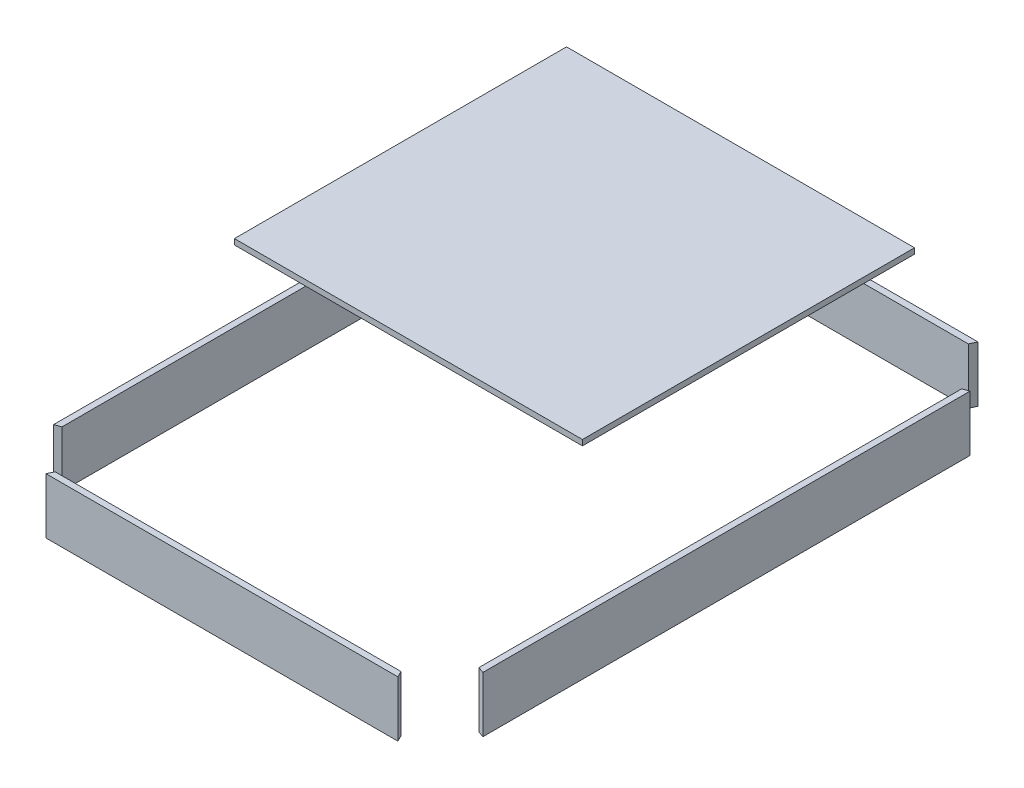
SolidWorks part; units mm, degrees
material "ABS"
ref_plane "Front Plane" through (0, 0, 0) normal (0, 0, 1) x (1, 0, 0)
ref_plane "Top Plane" through (0, 0, 0) normal (0, 1, 0) x (1, 0, 0)
ref_plane "Right Plane" through (0, 0, 0) normal (1, 0, 0) x (0, 0, -1)
sketch "Sketch2" plane through (0, 0, 0) normal (1, 0, 0) x (0, 0, -1)
  line L0 (0, 0) -> (-114.3, 0)
  line L1 (-114.3, 0) -> (-114.3, 25.4)
  line L2 (-114.3, 25.4) -> (-25.4, 50.8)
  line L3 (-25.4, 50.8) -> (94.742, 50.8)
  line L4 (114.3, 25.4) -> (114.3, 0)
  line L5 (114.3, 0) -> (0, 0)
  line L6 (-114.3, 25.4) -> (-114.3, 50.8)
  line L7 (-114.3, 50.8) -> (-25.4, 50.8)
  line L8 (114.3, 25.4) -> (94.742, 50.8)
  dimension "D1" = 25.4
  dimension "D2" = 25.4
  dimension "D3" = 114.3
  dimension "D4" = 114.3
  dimension "D5" = 88.9
  dimension "D6" = 94.742
ref_plane "Plane1" through (0, 25.4, 0) normal (0, 1, 0) x (1, 0, 0)
sketch "Sketch3" plane through (0, 25.4, 0) normal (0, 1, 0) x (1, 0, 0)
  line L0 (-34.4732, 114.3) -> (34.4732, 114.3)
  line L1 (0, 114.3) -> (0, 0) construction
  line L2 (50.8, 94.8425) -> (50.8, -94.8425)
  line L3 (50.8, -94.8425) -> (34.4732, -114.3)
  line L4 (34.4732, -114.3) -> (-34.4732, -114.3)
  line L5 (0, -114.3) -> (0, -25.4) construction
  line L6 (0, 114.3) -> (0, -114.3) construction
  line L7 (-50.8, -94.8425) -> (-34.4732, -114.3)
  line L8 (-50.8, 94.8425) -> (-50.8, -94.8425)
  line L9 (0, -114.3) -> (0, -95.25) construction
  line L10 (0, -95.25) -> (2.7232, -95.25) construction
  line L11 (2.7232, -95.25) -> (2.7232, -87.6586) construction
  line L12 (2.7232, -87.6586) -> (19.05, -68.2011) construction
  line L13 (19.05, -68.2011) -> (31.75, -68.2011) construction
  line L14 (31.75, -68.2011) -> (31.75, 0) construction
  line L15 (31.75, 0) -> (50.8, 0) construction
  line L16 (2.7232, -87.6586) -> (34.4732, -114.3) construction
  line L17 (19.05, -68.2011) -> (50.8, -94.8425) construction
  line L18 (0, 0) -> (-52.6953, 0) construction
  line L19 (50.8, 94.8425) -> (34.4732, 114.3)
  line L20 (-50.8, 94.8425) -> (-34.4732, 114.3)
  dimension "D1" = 101.6
  dimension "D2" = 12.7
  dimension "D3" = 40
  dimension "D4" = 19.05
  dimension "D5" = 19.05
  dimension "D6" = 25.4
ref_plane "Plane4" through (0, 0, -94.742) normal (0, 0, 1) x (1, 0, 0)
ref_plane "Plane2" through (0, 50.8, 0) normal (0, 1, 0) x (1, 0, 0)
sketch "Sketch4" plane through (0, 50.8, 0) normal (0, 1, 0) x (1, 0, 0)
  line L0 (-31.75, 94.742) -> (31.75, 94.742)
  line L1 (31.75, 94.742) -> (31.75, -25.4)
  line L3 (31.75, -25.4) -> (-31.75, -25.4)
  line L4 (0, 0) -> (0, -114.3) construction
  line L5 (0, 114.3) -> (0, -25.4) construction
  line L6 (-31.75, 94.742) -> (-31.75, -25.4)
  line L10 (31.75, -68.2011) -> (31.75, 0) construction
  point P3 (0, 0)
sketch "Sketch5" plane through (0, 0, 0) normal (0, 1, 0) x (1, 0, 0)
  line L0 (-50.8, -94.8425) -> (-34.4732, -114.3) construction
  line L1 (-50.8, 94.8425) -> (-50.8, -94.8425) construction
  line L4 (50.8, -94.8425) -> (34.4732, -114.3) construction
  line L5 (-50.8, 94.8425) -> (-34.4732, 114.3)
  line L6 (-50.8, -94.8425) -> (-34.4732, -114.3)
  line L7 (-50.8, 94.8425) -> (-50.8, -94.8425)
  line L9 (-34.4732, 114.3) -> (34.4732, 114.3)
  line L10 (50.8, -94.8425) -> (34.4732, -114.3)
  line L11 (-34.4732, -114.3) -> (34.4732, -114.3)
  line L12 (34.4732, 114.3) -> (50.8, 94.8425)
  line L13 (50.8, 94.8425) -> (50.8, -94.8425)
sketch "Sketch6" plane through (0, 25.4, 0) normal (0, 1, 0) x (1, 0, 0)
  line L0 (0, -114.3) -> (67.2604, -114.3)
sketch "Sketch9" plane through (0, 0, -94.742) normal (0, 0, 1) x (1, 0, 0)
  line L0 (31.75, 50.8) -> (50.8, 25.4)
  line L1 (31.75, 50.8) -> (-31.75, 50.8) construction
  line L2 (104.7751, 50.8) -> (-104.7751, 50.8) construction
  line L3 (50.8, 25.4) -> (34.4732, 25.4) construction
  line L4 (19.05, 25.4) -> (50.8, 25.4) construction
  line L5 (50.8, 25.4) -> (50.8, 0)
  line L6 (50.8, 0) -> (34.4732, 0) construction
  line L7 (-50.8, 0) -> (-50.8, 25.4)
  line L9 (-50.8, 25.4) -> (-34.4732, 25.4) construction
  line L10 (-34.4732, 25.4) -> (34.4732, 25.4) construction
  line L11 (-50.8, 25.4) -> (-31.75, 50.8)
  line L12 (-31.75, 50.8) -> (31.75, 50.8) construction
  dimension "D1" = 101.6
loft "Loft-Thin5" add profiles "Sketch5", "Sketch4" rebuild error yes
sketch "Sketch11" plane through (0, 50.8, 0) normal (0, 1, 0) x (1, 0, 0)
  line L1 (-79.2153, -47.1802) -> (79.375, -47.1802)
  line L2 (-79.2153, -47.1802) -> (-79.2153, 104.1552)
  line L3 (-79.2153, 104.1552) -> (79.375, 104.1552)
  line L4 (79.375, -47.1802) -> (79.375, 104.1552)
extrude "Boss-Extrude2" add sketch "Sketch11" along normal blind 2.54 from offset 2.54 offset against normal yes
sketch "Sketch12" plane through (0, 0, 0) normal (0, -1, 0) x (1, 0, 0)
  line L0 (-97.8074, -111.0383) -> (-94.9946, -109.9859)
  line L1 (-94.9946, -109.9859) -> (-94.9936, 109.9894)
  line L2 (-94.9936, 109.9894) -> (-97.814, 111.0114)
  line L3 (-97.814, 111.0114) -> (-97.8074, -111.0383)
  line L4 (-78.7991, 129.2837) -> (78.7991, 129.2837)
  line L5 (78.7991, 129.2837) -> (80.1661, 132.1045)
  line L6 (80.1661, 132.1045) -> (-80.1661, 132.1045)
  line L7 (-80.1661, 132.1045) -> (-78.7991, 129.2837)
  line L8 (94.9936, 109.9894) -> (97.814, 111.0114)
  line L9 (97.814, 111.0114) -> (97.8074, -111.0383)
  line L10 (97.8074, -111.0383) -> (94.9946, -109.9859)
  line L11 (94.9946, -109.9859) -> (94.9936, 109.9894)
  line L12 (78.796, -129.2688) -> (80.2007, -132.2581)
  line L13 (80.2007, -132.2581) -> (-80.2007, -132.2581)
  line L14 (-80.2007, -132.2581) -> (-78.796, -129.2688)
  line L15 (-78.796, -129.2688) -> (78.796, -129.2688)
extrude "Boss-Extrude3" add sketch "Sketch12" along normal blind 25.4
ref_plane "Plane5" through (0, 53.6755, 15.3358) normal (0, -0.9615, -0.2747) x (-1, 0, 0)
ref_plane "Plane13" through (0, 50.8, 0) normal (0, 1, 0) x (1, 0, 0)
sketch "Sketch13" plane through (0, 53.6755, 15.3358) normal (0, -0.9615, -0.2747) x (-1, 0, 0)
  line L0 (-173.1144, -114.6211) -> (93.5523, -114.6211) construction
  spline S0 degree 3 poles (54.4758, -49.9803) (54.9345, -46.6788) (51.1157, -47.6741) (35.7374, -48.1267) (25.5571, -59.1259) (14.5071, -61.2429) (7.8812, -57.8641) (4.2982, -57.6207) (0.6427, -58.7127) (-3.2392, -57.9091) (-6.4713, -59.2889) (-11.4837, -57.7632) (-11.5936, -60.6849) (-20.1052, -60.6678) (-25.9321, -56.4087) (-33.4738, -51.8484) (-39.9945, -47.0959) (-53.504, -46.569) (-54.2725, -51.2584) (-43.0531, -51.4718) (-35.8641, -55.4485) (-32.6844, -58.2169) (-26.6223, -63.365) (-20.3239, -65.156) (-21.4624, -67.078) (-25.152, -68.6739) (-25.5328, -71.3089) (-21.0251, -73.4452) (-14.6492, -72.6338) (-11.5324, -68.2831) (-11.6484, -74.1266) (-10.4817, -78.7057) (-6.7781, -82.7312) (-5.6408, -90.1916) (-8.3489, -96.5667) (-4.8863, -101.6725) (4.3644, -101.7808) (6.6986, -100.2173) (8.8744, -93.9188) (4.436, -86.9808) (10.7498, -79.5114) (12.972, -74.6824) (11.0693, -67.8183) (19.2545, -75.6984) (26.3261, -71.163) (26.1483, -68.5132) (17.0818, -65.3783) (25.8696, -64.3189) (31.9453, -59.3666) (34.1208, -56.6324) (41.3974, -52.9134) (47.0273, -51.4712) (53.9956, -51.1847) (54.4758, -49.9803) (54.9345, -46.6788) (51.1157, -47.6741) knots -0.023666 -0.019222 -0.002136 0 0.079284 0.108848 0.295642 0.378737 0.390366 0.411926 0.437324 0.452431 0.475363 0.496045 0.519743 0.526703 0.561311 0.570129 0.610557 0.63735 0.642843 0.662971 0.668219 0.690069 0.694419 0.707366 0.711406 0.730777 0.735652 0.755275 0.759572 0.776169 0.792617 0.796867 0.816246 0.819679 0.828773 0.838814 0.841038 0.849905 0.851507 0.855955 0.864379 0.866027 0.872435 0.88205 0.889596 0.892036 0.906451 0.923904 0.928816 0.952595 0.957874 0.976334 0.980778 0.997864 1 1.079284 1.108848 1.295642 only from (54.5731, -49.2668) to (54.5731, -49.2668)
extrude "Cut-Extrude1" cut sketch "Sketch13" against normal through all both and the other way through all rebuild error yes
sketch "Sketch22" plane through (0, 50.8, 0) normal (0, 1, 0) x (1, 0, 0)
  line L0 (0, 0) -> (0, 105.376) construction
  line L1 (35.1719, 0) -> (64.5011, 18.2506)
  line L3 (37.8558, -4.3131) -> (67.185, 13.9375)
  spline S0 degree 3 poles (54.631, 104.7157) (45.5254, 104.8181) (36.4206, 104.9725) (18.2107, 105.2534) (9.1051, 105.376) (-9.1056, 105.376) (-18.2109, 105.2534) (-36.4208, 104.9725) (-45.5255, 104.8181) (-54.631, 104.7157) knots 0 0 0 0 0.25 0.25 0.5 0.5 0.75 0.75 1 1 1 1 construction
  dimension "D1" = 34.544
  dimension "D2" = 5.08
ref_plane "Plane7" through (0, 0, 0) normal (1, 0, 0) x (0, 0, -1)
ref_plane "Plane8" through (0, 46.99, 0) normal (0, 1, 0) x (1, 0, 0)
ref_plane "Plane16" through (94.9941, 0, 0.0004) normal (-1, 0, 0) x (0, 0, 1)
ref_plane "Plane9" through (0, 0, 129.2837) normal (0, 0, -1) x (-1, 0, 0)
sketch "Sketch25" plane through (0, 0, 129.2837) normal (0, 0, -1) x (-1, 0, 0)
  line L0 (-48.5711, 50.8) -> (-20.5879, 50.8) construction
  line L1 (-78.7991, -25.4) -> (-94.9936, -25.4) construction
  dimension "D1" = 76.2
sketch "Sketch26" plane through (0, 46.99, 0) normal (0, 1, 0) x (1, 0, 0)
  line L0 (34.5796, -119.7209) -> (54.7931, -97.4321)
  line L4 (94.9944, 69.8816) -> (94.9938, -69.8825) construction
  line L5 (49.8393, -129.2837) -> (-49.8393, -129.2837) construction
  circle A1 centre (54.7931, -97.4321) radius 3.429
  dimension "D2" = 6.858
  dimension "D3" = 31.8516
  dimension "D1" = 40.2006
extrude "Cut-Extrude5" cut sketch "Sketch26" against normal through all both and the other way through all contours A1 rebuild error yes
mirror "Mirror2" about plane through (0, 0, 0) normal (1, 0, 0) rebuild error yes
ref_plane "Plane11" through (0, 0, -132.2581) normal (0, 0, -1) x (-1, 0, 0)
sketch "Sketch27" plane through (0, 0, -132.2581) normal (0, 0, -1) x (-1, 0, 0)
  line L0 (80.2007, 0) -> (-80.2007, 0) construction
  line L2 (-41.91, 0) -> (41.91, 0)
  line L3 (44.45, 2.54) -> (44.45, 22.86)
  line L4 (41.91, 25.4) -> (-41.91, 25.4)
  line L5 (0, 25.4) -> (0, 0) construction
  line L6 (-44.45, 2.54) -> (-44.45, 22.86)
  arc A0 (41.91, 0) -> (44.45, 2.54) centre (41.91, 2.54) ccw
  arc A1 (-44.45, 2.54) -> (-41.91, 0) centre (-41.91, 2.54) ccw
  arc A2 (-44.45, 22.86) -> (-41.91, 25.4) centre (-41.91, 22.86) cw
  arc A3 (44.45, 22.86) -> (41.91, 25.4) centre (41.91, 22.86) ccw
  point P10 (44.45, 0)
  point P13 (-44.45, 0)
  point P16 (-44.45, 25.4)
  point P19 (44.45, 25.4)
  dimension "D1" = 2.54
extrude "Cut-Extrude6" cut sketch "Sketch27" against normal blind 7.62 contours L4 A2 L6 A1 L2 A0 L3 A3 rebuild error yes
ref_plane "Plane14" through (9.8176, 0, 15.7771) normal (0.5283, 0, 0.849) x (0.849, 0, -0.5283)
sketch "Sketch29" plane through (9.8176, 0, 15.7771) normal (0.5283, 0, 0.849) x (0.849, 0, -0.5283)
  line L0 (64.4063, 50.8) -> (64.4063, 53.34)
  line L1 (64.4063, 53.34) -> (29.8623, 53.34)
  line L2 (29.8623, 50.8) -> (29.8623, 53.34)
  line L3 (29.8623, 50.8) -> (64.4063, 50.8)
ref_plane "Plane15" through (13.2359, 50.1049, 21.2705) normal (0.2363, 0.8944, 0.3797) x (0.9717, -0.2175, -0.0923)
sketch "Sketch30" plane through (13.2359, 50.1049, 21.2705) normal (0.2363, 0.8944, 0.3797) x (0.9717, -0.2175, -0.0923)
  line L1 (37.6671, 29.2432) -> (40.4292, 24.2805)
  line L2 (52.759, 37.643) -> (22.5752, 20.8435) construction
  line L4 (25.3373, 15.8807) -> (55.5211, 32.6802) construction
  line L5 (40.4292, 24.2805) -> (41.9959, 21.4656)
  point P4 (37.6671, 29.2432)
  point P14 (40.4292, 24.2805)
sweep "Cut-Sweep3" cut profiles "Sketch29" path "Sketch30" rebuild error yes
pattern_linear "LPattern1" count 10 spacing 7.62 rebuild error yes
mirror "Mirror3" about plane through (0, 0, 0) normal (1, 0, 0) rebuild error yes
ref_plane "Plane17" through (0, 0, -129.2688) normal (0, 0, 1) x (1, 0, 0)
ref_plane "Plane18" through (-94.9941, 0, 0.0004) normal (1, 0, 0) x (0, 0, -1)
sketch "Sketch32" plane through (0, 50.8, 0) normal (0, 1, 0) x (1, 0, 0)
  line L0 (-13.97, 129.2688) -> (13.97, 129.2688) construction
  line L1 (-94.9941, -13.9704) -> (-94.9942, 13.9696) construction
  line L2 (0, 105.376) -> (0, 0) construction
  circle A0 centre (-53.8973, 92.8706) radius 3.429
  circle A1 centre (53.8973, 92.8706) radius 3.429
  dimension "D3" = 6.858
  dimension "D1" = 36.3982
  dimension "D2" = 41.0972
extrude "Cut-Extrude7" cut sketch "Sketch32" against normal through all both and the other way through all rebuild error yes
ref_plane "Plane19" through (0, 0, 132.1045) normal (0, 0, 1) x (1, 0, 0)
sketch "Sketch33" plane through (0, 0, 132.1045) normal (0, 0, 1) x (1, 0, 0)
  line L0 (80.1661, -25.4) -> (-80.1661, -25.4) construction
  line L1 (16.6661, -25.4) -> (-23.0161, -25.4)
  line L2 (16.6661, -25.4) -> (16.6661, 11.4171)
  line L3 (16.6661, 11.4171) -> (-23.0161, 11.4171)
  line L4 (-23.0161, -25.4) -> (-23.0161, 11.4171)
  line L5 (80.1661, -25.4) -> (80.1661, 0) construction
  line L6 (-80.1661, -25.4) -> (-80.1661, 0) construction
  dimension "D1" = 63.5
  dimension "D2" = 57.15
extrude "Cut-Extrude8" cut sketch "Sketch33" against normal up to surface (261.3733 mm away) rebuild error yes up to face at (0, -12.7, -129.2688)
